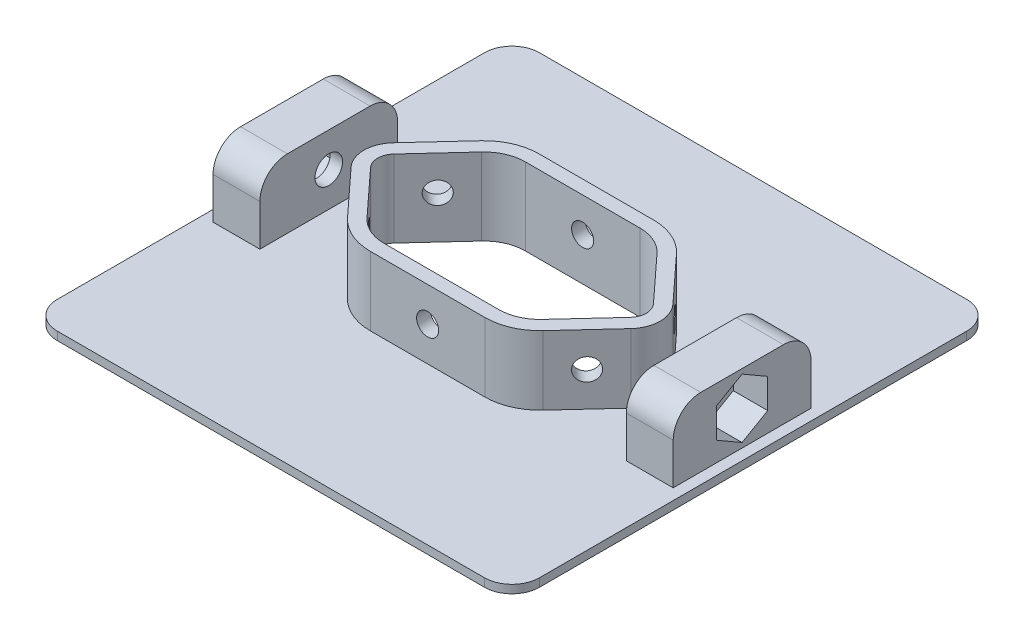
SolidWorks part; units mm, degrees
ref_plane "Front Plane" through (0, 0, 0) normal (0, 0, 1) x (1, 0, 0)
ref_plane "Top Plane" through (0, 0, 0) normal (0, 1, 0) x (1, 0, 0)
ref_plane "Right Plane" through (0, 0, 0) normal (1, 0, 0) x (0, 0, -1)
sketch "Sketch1" plane through (0, 0, 0) normal (0, 1, 0) x (1, 0, 0)
  line L1 (-35, -35) -> (35, -35)
  line L2 (-35, -35) -> (-35, 35)
  line L3 (-35, 35) -> (35, 35)
  line L4 (35, -35) -> (35, 35)
  line L5 (-35, -35) -> (35, 35) construction
  line L6 (-35, 35) -> (35, -35) construction
  point P0 (0, 0)
  dimension "D1" = 70
  dimension "D2" = 70
extrude "Boss-Extrude1" add sketch "Sketch1" along normal blind 1.2
fillet "Fillet1" radius 4 4 edges at (-35, 0.6, -35) (-35, 0.6, 35) (35, 0.6, -35) (35, 0.6, 35)
sketch "Sketch3" plane through (0, 1.2, 0) normal (0, 1, 0) x (1, 0, 0)
  line L0 (-35, 0) -> (-33.4, 0)
  line L1 (-35, 31) -> (-35, -31) construction
  line L4 (-33.4, -10) -> (-26.6, -10)
  line L5 (-33.4, -10) -> (-33.4, 10)
  line L6 (-33.4, 10) -> (-26.6, 10)
  line L7 (-26.6, -10) -> (-26.6, 10)
  line L8 (35, 0) -> (33.4, 0)
  line L9 (35, -31) -> (35, 31) construction
  line L11 (33.4, 10) -> (26.6, 10)
  line L12 (26.6, -10) -> (26.6, 10)
  line L13 (33.4, -10) -> (26.6, -10)
  line L14 (33.4, -10) -> (33.4, 10)
  dimension "D1" = 20
  dimension "D2" = 6.8
  dimension "D3" = 6.8
  dimension "D4" = 1.6
  dimension "D5" = 1.6
extrude "Boss-Extrude3" add sketch "Sketch3" along normal blind 10 contours L4 L7 L6 L5 | L13 L14 L11 L12 region at (-30, 1.2, 0) region at (30, 1.2, 0)
fillet "Fillet2" radius 4 4 edges at (30, 11.2, -10) (30, 11.2, 10) (-30, 11.2, 10) (-30, 11.2, -10)
sketch "Sketch4" plane through (-33.4, 0, 0) normal (-1, 0, 0) x (0, 0, 1)
  line L0 (0, 11.2) -> (0, 1.2)
  line L1 (6, 11.2) -> (-6, 11.2) construction
  line L2 (10, 1.2) -> (-10, 1.2) construction
  line L4 (0, 10.5) -> (-3.7239, 8.35)
  line L5 (-3.7239, 8.35) -> (-3.7239, 4.05)
  line L6 (-3.7239, 4.05) -> (0, 1.9)
  line L7 (0, 1.9) -> (3.7239, 4.05)
  line L8 (3.7239, 4.05) -> (3.7239, 8.35)
  line L9 (3.7239, 8.35) -> (0, 10.5)
  circle A0 centre (0, 6.2) radius 4.3 construction
  circle A1 centre (0, 6.2) radius 2
extrude "Cut-Extrude1" cut sketch "Sketch4" against normal blind 5 contours L5 L6 L0 L4 | L8 L9 L0 L7 region at (-33.4, 9.3438, 1.8151) region at (-33.4, 9.35, -0.0937)
sketch "Sketch5" plane through (0, 1.2, 0) normal (0, 1, 0) x (1, 0, 0)
  line L0 (18.8382, 1.6944) -> (12.7344, 8.3165)
  line L1 (8.3226, 10.25) -> (-8.3226, 10.25)
  line L2 (-12.7344, 8.3165) -> (-18.8382, 1.6944)
  line L3 (-12.7344, -8.3165) -> (-18.8382, -1.6944)
  line L4 (8.3226, -10.25) -> (-8.3226, -10.25)
  line L5 (18.8382, -1.6944) -> (12.7344, -8.3165)
  line L6 (20.3088, 3.0499) -> (14.205, 9.672)
  line L7 (8.3226, 12.25) -> (-8.3226, 12.25)
  line L8 (-14.205, 9.672) -> (-20.3088, 3.0499)
  line L9 (-14.205, -9.672) -> (-20.3088, -3.0499)
  line L10 (8.3226, -12.25) -> (-8.3226, -12.25)
  line L11 (20.3088, -3.0499) -> (14.205, -9.672)
  arc A0 (12.7344, 8.3165) -> (8.3226, 10.25) centre (8.3226, 4.25) ccw
  arc A1 (-8.3226, 10.25) -> (-12.7344, 8.3165) centre (-8.3226, 4.25) ccw
  arc A2 (-18.8382, 1.6944) -> (-18.8382, -1.6944) centre (-17, 0) ccw
  arc A3 (-8.3226, -10.25) -> (-12.7344, -8.3165) centre (-8.3226, -4.25) cw
  arc A4 (12.7344, -8.3165) -> (8.3226, -10.25) centre (8.3226, -4.25) cw
  arc A5 (18.8382, 1.6944) -> (18.8382, -1.6944) centre (17, 0) cw
  arc A6 (14.205, 9.672) -> (8.3226, 12.25) centre (8.3226, 4.25) ccw
  arc A7 (-8.3226, 12.25) -> (-14.205, 9.672) centre (-8.3226, 4.25) ccw
  arc A8 (-20.3088, 3.0499) -> (-20.3088, -3.0499) centre (-17, 0) ccw
  arc A9 (-8.3226, -12.25) -> (-14.205, -9.672) centre (-8.3226, -4.25) cw
  arc A10 (14.205, -9.672) -> (8.3226, -12.25) centre (8.3226, -4.25) cw
  arc A11 (20.3088, 3.0499) -> (20.3088, -3.0499) centre (17, 0) cw
extrude "Cut-Extrude2" cut sketch "Sketch5" against normal through all contours L1 A1 L2 A2 L3 A3 L4 A4 L5 A5 L0 A0
extrude "Boss-Extrude4" add sketch "Sketch5<3>" along normal blind 10
sketch "Sketch5<3>" plane through (0, 1.2, 0) normal (0, 1, 0) x (1, 0, 0) same geometry as "Sketch5"
sketch "Sketch6" plane through (0, 0, 12.25) normal (0, 0, 1) x (1, 0, 0)
  line L0 (0, 11.2) -> (0, 1.2) construction
  line L1 (-8.3226, 11.2) -> (8.3226, 11.2) construction
  line L2 (-8.3226, 1.2) -> (8.3226, 1.2) construction
  circle A0 centre (0, 6.2) radius 1.6
extrude "Cut-Extrude4" cut sketch "Sketch6" against normal up to surface (24.5 mm away) up to face at (0, 6.2, -12.25)
sketch "Sketch7" plane through (-12.5, 0, 11.5217) normal (-0.7353, 0, 0.6777) x (0.6777, 0, 0.7353)
  line L0 (-7.0187, 11.2) -> (-7.0187, 1.2) construction
  line L1 (-11.5217, 11.2) -> (-2.5156, 11.2) construction
  line L2 (-11.5217, 1.2) -> (-2.5156, 1.2) construction
  circle A0 centre (-7.0187, 6.2) radius 1.6
extrude "Cut-Extrude5" cut sketch "Sketch7" against normal up to next
sketch "Sketch8" plane through (12.5, 0, 11.5217) normal (0.7353, 0, 0.6777) x (0.6777, 0, -0.7353)
  line L0 (7.0187, 11.2) -> (7.0187, 1.2) construction
  line L1 (2.5156, 11.2) -> (11.5217, 11.2) construction
  line L2 (2.5156, 1.2) -> (11.5217, 1.2) construction
  circle A0 centre (7.0187, 6.2) radius 1.6
extrude "Cut-Extrude6" cut sketch "Sketch8" against normal up to next
sketch "Sketch9" plane through (-12.5, 0, -11.5217) normal (-0.7353, 0, -0.6777) x (-0.6777, 0, 0.7353)
  line L0 (7.0187, 11.2) -> (7.0187, 1.2) construction
  line L1 (2.5156, 11.2) -> (11.5217, 11.2) construction
  line L2 (2.5156, 1.2) -> (11.5217, 1.2) construction
  circle A0 centre (7.0187, 6.2) radius 1.6
extrude "Cut-Extrude7" cut sketch "Sketch9" against normal up to next
sketch "Sketch10" plane through (12.5, 0, -11.5217) normal (0.7353, 0, -0.6777) x (-0.6777, 0, -0.7353)
  line L0 (-7.0187, 11.2) -> (-7.0187, 1.2) construction
  line L1 (-11.5217, 11.2) -> (-2.5156, 11.2) construction
  line L2 (-11.5217, 1.2) -> (-2.5156, 1.2) construction
  circle A0 centre (-7.0187, 6.2) radius 1.6
extrude "Cut-Extrude8" cut sketch "Sketch10" against normal up to next
sketch "Sketch13" plane through (-33.4, 0, 0) normal (-1, 0, 0) x (0, 0, 1)
  circle A0 centre (0, 6.2) radius 2
extrude "Cut-Extrude10" cut sketch "Sketch13" against normal up to surface (6.8 mm away) up to face at (-26.6, 6.8095, 0)
sketch "Sketch14" plane through (33.4, 0, 0) normal (1, 0, 0) x (0, 0, -1)
  line L0 (0, 11.2) -> (0, 1.2)
  line L1 (0, 10.5) -> (-3.7239, 8.35)
  line L2 (-3.7239, 8.35) -> (-3.7239, 4.05)
  line L3 (-3.7239, 4.05) -> (0, 1.9)
  line L4 (0, 1.9) -> (3.7239, 4.05)
  line L5 (3.7239, 4.05) -> (3.7239, 8.35)
  line L6 (3.7239, 8.35) -> (0, 10.5)
  line L7 (-6, 11.2) -> (6, 11.2)
  line L8 (-6, 11.2) -> (6, 11.2) construction
  circle A0 centre (0, 6.2) radius 4.3 construction
  arc A1 (-6, 11.2) -> (-10, 7.2) centre (-6, 7.2) ccw construction
  circle A2 centre (0, 6.2) radius 2
extrude "Cut-Extrude11" cut sketch "Sketch14" against normal blind 5 contours A2 L0 L4 L5 L6 | A2 L0 L1 L2 L3 region at (33.4, 9.3438, -1.8151) region at (33.4, 9.35, 0.0937)
extrude "Cut-Extrude12" cut sketch "Sketch14<4>" against normal up to surface (6.8 mm away) contours L0 A2 | L0 A2 region at (33.4, 6.2, -0.8488) region at (33.4, 6.2, 0.8488) up to face at (26.6, 6.8095, 0)
sketch "Sketch14<4>" plane through (33.4, 0, 0) normal (1, 0, 0) x (0, 0, -1) same geometry as "Sketch14"
